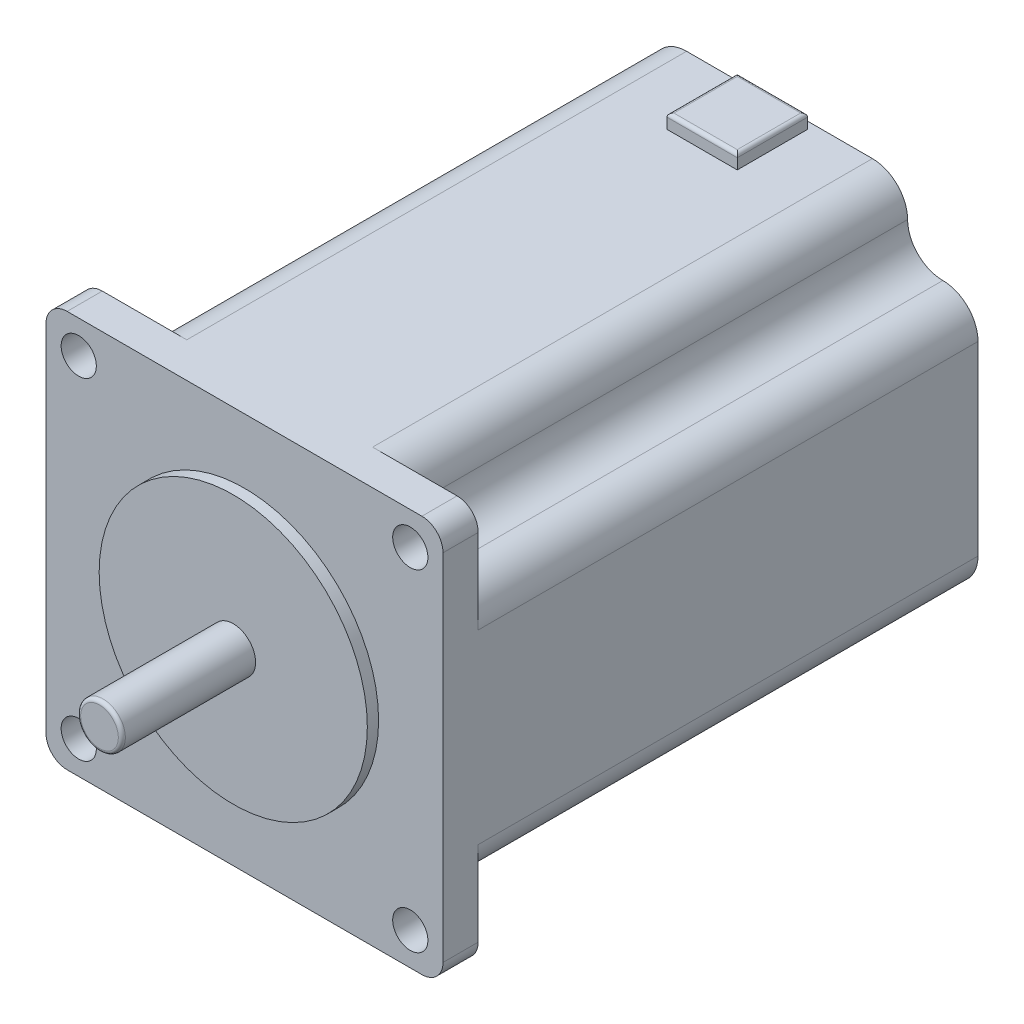
SolidWorks part; units mm, degrees
material "Серое литое железо (SN)"
ref_plane "Спереди" through (0, 0, 0) normal (0, 0, 1) x (1, 0, 0)
ref_plane "Сверху" through (0, 0, 0) normal (0, 1, 0) x (1, 0, 0)
ref_plane "Справа" through (0, 0, 0) normal (1, 0, 0) x (0, 0, -1)
sketch "Эскиз1" plane through (0, 0, 0) normal (0, 0, 1) x (1, 0, 0)
  line L1 (-28.2, 28.2) -> (28.2, 28.2)
  line L2 (-28.2, 28.2) -> (-28.2, -28.2)
  line L3 (-28.2, -28.2) -> (28.2, -28.2)
  line L4 (28.2, 28.2) -> (28.2, -28.2)
  line L5 (-28.2, 28.2) -> (28.2, -28.2) construction
  line L6 (-28.2, -28.2) -> (28.2, 28.2) construction
  point P0 (0, 0)
  dimension "D1" = 56.4
  dimension "D2" = 56.4
extrude "Бобышка-Вытянуть1" add sketch "Эскиз1" along normal blind 76
sketch "Эскиз2" plane through (0, 0, 76) normal (0, 0, 1) x (1, 0, 0)
  circle A0 centre (0, 0) radius 19.05
extrude "Бобышка-Вытянуть2" add sketch "Эскиз2" along normal blind 1.6
sketch "Эскиз3" plane through (0, 0, 77.6) normal (0, 0, 1) x (1, 0, 0)
  circle A0 centre (0, 0) radius 3.175
extrude "Бобышка-Вытянуть3" add sketch "Эскиз3" along normal blind 19
sketch "Эскиз4" plane through (0, 0, 0) normal (0, 0, -1) x (-1, 0, 0)
  circle A0 centre (0, 0) radius 3.175
extrude "Вырез-Вытянуть1" cut sketch "Эскиз4" against normal blind 0.5
sketch "Эскиз6" plane through (0, 0, 0) normal (0, 0, -1) x (-1, 0, 0)
  line L1 (-28.2, 28.2) -> (-18.2, 28.2)
  line L2 (-28.2, 28.2) -> (-28.2, 18.2)
  line L3 (-28.2, 18.2) -> (-18.2, 18.2)
  line L4 (-18.2, 28.2) -> (-18.2, 18.2)
  dimension "D1" = 10
  dimension "D2" = 10
extrude "Вырез-Вытянуть2" cut sketch "Эскиз6" against normal blind 71
pattern_linear "Линейный массив1" count 2 spacing 46.4 along (-1, 0, 0) count 2 spacing 46.4 along (0, -1, 0) of "Вырез-Вытянуть2"
fillet "Скругление1" radius 5 12 edges at (-28.2, 18.2, 35.5) (-28.2, -18.2, 35.5) (-18.2, -28.2, 35.5) (18.2, -28.2, 35.5) (28.2, -18.2, 35.5) (28.2, 18.2, 35.5) (-18.2, 28.2, 35.5) (18.2, 28.2, 35.5) (18.2, -18.2, 35.5) (-18.2, -18.2, 35.5) (-18.2, 18.2, 35.5) (18.2, 18.2, 35.5)
sketch "Эскиз7" plane through (0, 0, 76) normal (0, 0, 1) x (1, 0, 0)
  line L0 (-23.55, 32.8955) -> (-23.55, -33.1396) construction
  line L1 (34.9254, 23.55) -> (-37.2729, 23.55) construction
  line L2 (23.55, 32.8955) -> (23.55, -33.1396) construction
  line L3 (34.9254, -23.55) -> (-37.2729, -23.55) construction
  line L4 (28.2, -28.2) -> (28.2, 28.2) construction
  line L5 (28.2, 28.2) -> (-28.2, 28.2) construction
  circle A0 centre (-23.55, 23.55) radius 2.5
  dimension "D1" = 47.1
  dimension "D2" = 47.1
  dimension "D3" = 4.65
  dimension "D4" = 4.65
extrude "Вырез-Вытянуть3" cut sketch "Эскиз7" against normal blind 71
pattern_linear "Линейный массив2" count 2 spacing 47.1 along (1, 0, 0) count 2 spacing 47.1 along (0, -1, 0) of "Вырез-Вытянуть3"
fillet "Скругление2" radius 3 4 edges at (-28.2, -28.2, 73.5) (28.2, -28.2, 73.5) (28.2, 28.2, 73.5) (-28.2, 28.2, 73.5)
fillet "Скругление3" radius 0.5 1 edges at (3.175, 0, 96.6)
sketch "Эскиз8" plane through (0, 28.2, 0) normal (0, 1, 0) x (1, 0, 0)
  line L0 (13.2, 0) -> (-13.2, 0) construction
  line L1 (-5, -1) -> (5, -1)
  line L2 (-5, -1) -> (-5, -11)
  line L3 (-5, -11) -> (5, -11)
  line L4 (5, -1) -> (5, -11)
  line L5 (-5, -1) -> (5, -11) construction
  line L6 (-5, -11) -> (5, -1) construction
  point P0 (0, -6)
  dimension "D1" = 10
  dimension "D2" = 10
  dimension "D3" = 1
  dimension "D4" = 0
extrude "Бобышка-Вытянуть4" add sketch "Эскиз8" along normal blind 2
fillet "Скругление4" radius 0.5 4 edges at (0, 30.2, 11) (-5, 30.2, 6) (0, 30.2, 1) (5, 30.2, 6)
